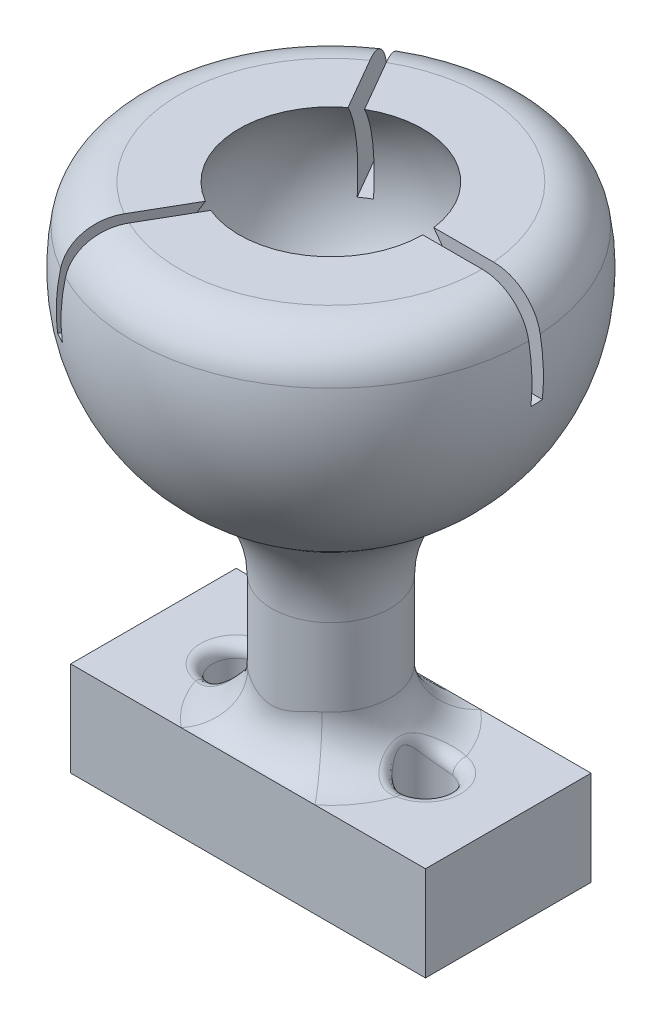
SolidWorks part; units mm, degrees
ref_plane "Front Plane" through (0, 0, 0) normal (0, 0, 1) x (1, 0, 0)
ref_plane "Top Plane" through (0, 0, 0) normal (0, 1, 0) x (1, 0, 0)
ref_plane "Right Plane" through (0, 0, 0) normal (1, 0, 0) x (0, 0, -1)
sketch "Sketch1" plane through (0, 0, 0) normal (0, 0, 1) x (1, 0, 0)
  line L0 (0, 0) -> (0, 3.5) construction
  line L1 (0, 3.5) -> (0, 8.5) construction
  line L2 (0, 8.5) -> (0, 13.5) construction
  line L3 (0, 13.5) -> (0, 17) construction
  line L4 (0, 17) -> (0, 13.5)
  line L5 (0, 3.5) -> (0, 0)
  arc A0 (0, 3.5) -> (0, 13.5) centre (0, 8.5) cw
  arc A1 (0, 17) -> (0, 0) centre (0, 8.5) ccw
  dimension "D1" = 3.5
  dimension "D2" = 5
  dimension "D3" = 5
  dimension "D4" = 3.5
revolve "Revolve1" add sketch "Sketch1" angle 360 about L2
sketch "Sketch3" plane through (0, 0, 0) normal (0, 1, 0) x (1, 0, 0)
  circle A0 centre (0, 0) radius 2.5
extrude "Boss-Extrude1" add sketch "Sketch3" against normal blind 13 from offset 1
sketch "Sketch4" plane through (0, -12, 0) normal (0, -1, 0) x (1, 0, 0)
  line L1 (-7.5, 3.5) -> (7.5, 3.5)
  line L2 (-7.5, 3.5) -> (-7.5, -3.5)
  line L3 (-7.5, -3.5) -> (7.5, -3.5)
  line L4 (7.5, 3.5) -> (7.5, -3.5)
  line L5 (-7.5, 3.5) -> (7.5, -3.5) construction
  line L6 (-7.5, -3.5) -> (7.5, 3.5) construction
  point P0 (0, 0)
  dimension "D1" = 15
  dimension "D2" = 7
extrude "Boss-Extrude2" add sketch "Sketch4" against normal blind 4
sketch "Sketch5" plane through (0, -12, 0) normal (0, -1, 0) x (1, 0, 0)
  line L0 (7.5, 3.5) -> (-7.5, 3.5) construction
  circle A0 centre (-4, 0) radius 1
  circle A1 centre (4, 0) radius 1
  dimension "D1" = 3.5
  dimension "D2" = 3.5
  dimension "D3" = 4
  dimension "D4" = 4
extrude "Cut-Extrude1" cut sketch "Sketch5" against normal blind 4
sketch "Sketch6" plane through (0, 0, 0) normal (0, 1, 0) x (1, 0, 0)
  circle A0 centre (0, 0) radius 9
extrude "Cut-Extrude2" cut sketch "Sketch6" along normal blind 6 from offset 11.65
sketch "Sketch7" plane through (0, 11.65, 0) normal (0, 1, 0) x (1, 0, 0)
  line L1 (0, 0) -> (10, 0)
  line L2 (0, 0) -> (0, 0.5)
  line L3 (0, 0.5) -> (10, 0.5)
  line L4 (10, 0) -> (10, 0.5)
  dimension "D1" = 10
  dimension "D2" = 0.5
extrude "Cut-Extrude3" cut sketch "Sketch7" against normal blind 4
pattern_circular "CirPattern1" count 3 over 360 about axis through (0, 0, 0) along (0, 1, 0) of "Cut-Extrude3"
fillet "Fillet1" radius 2 1 edges at (0, -8, -2.5)
sketch "Sketch10" plane through (0, 0, 0) normal (1, 0, 0) x (0, 0, -1)
  line L0 (-8.4987, 8.35) -> (8.4987, 8.35) construction
  line L1 (0, 8.35) -> (-7.8948, 11.65) construction
  line L2 (-7.8948, 11.65) -> (-7.8948, 8.35) construction
  arc A0 (-7.8948, 11.65) -> (-2.5, 0.376) centre (0, 8.5) ccw construction
  arc A1 (2.5, 0.376) -> (7.8948, 11.65) centre (0, 8.5) ccw construction
  dimension "D1" = 3.3
  dimension "D2" = 8.5567
fillet "Fillet2" radius 5 1 edges at (0, 0.376, 2.5)
fillet "Fillet3" radius 2 3 edges at (3.7288, 11.65, -6.9587) (4.162, 11.65, 6.7086) (-7.8908, 11.65, 0.2501)
sketch "Sketch11" plane through (0, -12, 0) normal (0, -1, 0) x (1, 0, 0)
  circle A0 centre (-4, 0) radius 1.9
  circle A1 centre (4, 0) radius 1.9
fillet "Fillet4" radius 0.5 6 edges at (3, -7.3229, -0.0099) (-3, -7.3229, 0.0099) (-5, -8, 0) (-4, -12, -1) (5, -8, 0) (4, -12, -1)
